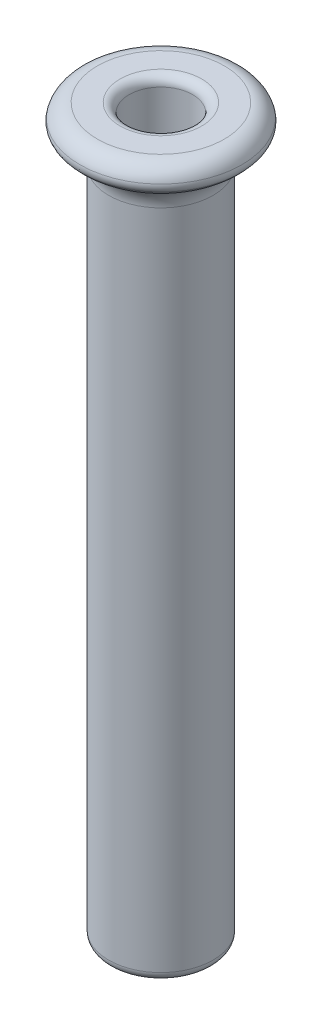
SolidWorks part; units mm, degrees
ref_plane "Front Plane" through (0, 0, 0) normal (0, 0, 1) x (1, 0, 0)
ref_plane "Top Plane" through (0, 0, 0) normal (0, 1, 0) x (1, 0, 0)
ref_plane "Right Plane" through (0, 0, 0) normal (1, 0, 0) x (0, 0, -1)
sketch "Sketch1" plane through (0, 0, 0) normal (0, 0, 1) x (1, 0, 0)
  line L0 (0, 0) -> (0, -12.846) construction
  line L1 (2.6, 0) -> (9, 0)
  line L2 (9, 0) -> (9, -3)
  line L3 (9, -3) -> (5.75, -3)
  line L4 (5.75, -3) -> (5.75, -80)
  line L5 (5.75, -80) -> (2.6, -80)
  line L6 (2.6, -80) -> (2.6, 0)
  line L7 (0, -8) -> (2.6, -8)
  line L9 (0, 0) -> (3.5, 0)
  line L10 (0, 0) -> (0, -8)
  line L11 (0, -8) -> (3.5, -8)
  line L12 (3.5, 0) -> (3.5, -8)
  dimension "D1" = 3.25
  dimension "D2" = 6.4
  dimension "D3" = 80
  dimension "D4" = 3
  dimension "D5" = 2.6
  dimension "D6" = 3.5
  dimension "D7" = 8
revolve "Revolve1" add sketch "Sketch1" angle 360 about L0
fillet "Fillet1" radius 3 1 edges at (-5.75, -3, 0) type face fillet first side face at (-5.75, -3, 0) second side face at (-5.75, -80, 0)
fillet "Fillet3" radius 2 1 edges at (-9, 0, 0)
fillet "Fillet4" radius 1 1 edges at (-3.5, 0, 0)
fillet "Fillet7" radius 0.5 1 edges at (-2.6, -8, 0) type face fillet first side face at (-3.5, -8, 0) second side face at (-2.6, -8, 0)
fillet "Fillet9" radius 1 1 edges at (-2.6, -80, 0) type face fillet first side face at (-2.6, -80, 0) second side face at (-2.6, -8.5, 0)
fillet "Fillet10" radius 1 1 edges at (-5.75, -80, 0) type face fillet first side face at (3.6, -80, 0) second side face at (5.75, -6, 0)
fillet "Fillet11" radius 3 1 edges at (-9, -3, 0)
fillet "Fillet12" radius 1 1 edges at (-9, -2, 0)
fillet "Fillet13" radius 1 1 edges at (-3.5, -8, 0)
